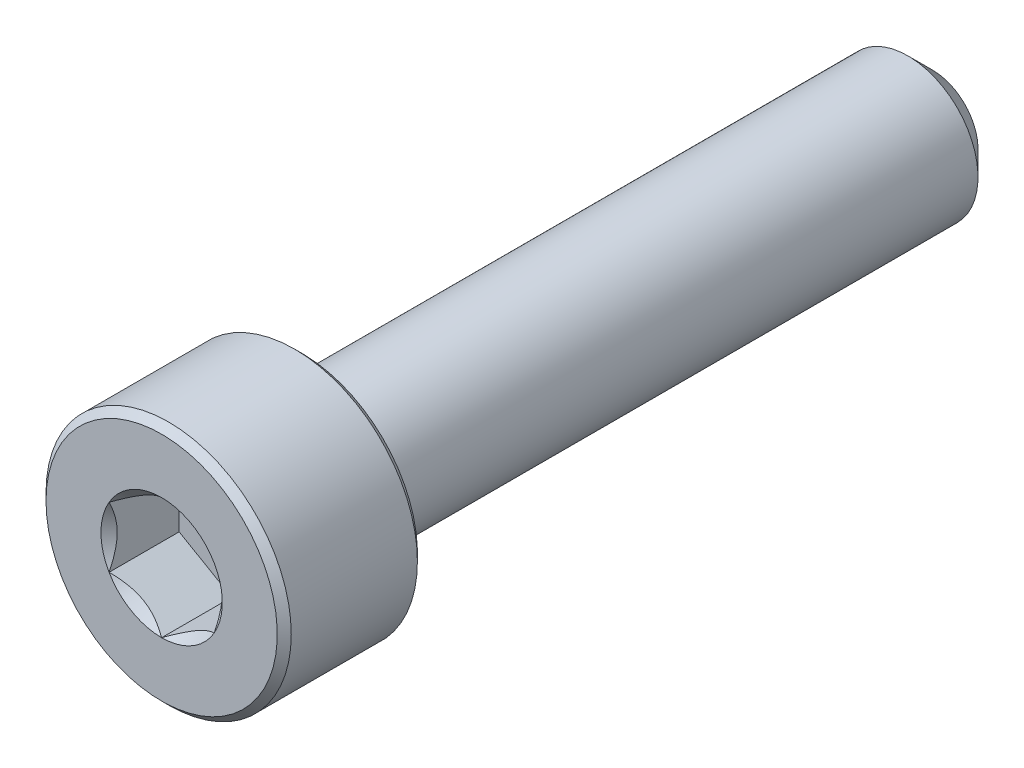
SolidWorks part; units mm, degrees
material "Plain Carbon Steel"
ref_plane "Front Plane" through (0, 0, 0) normal (0, 0, 1) x (1, 0, 0)
ref_plane "Top Plane" through (0, 0, 0) normal (0, 1, 0) x (1, 0, 0)
ref_plane "Right Plane" through (0, 0, 0) normal (1, 0, 0) x (0, 0, -1)
sketch "Sketch1" plane through (0, 0, 0) normal (1, 0, 0) x (0, 0, -1)
  line L0 (-11, 0) -> (11, 0) construction
  line L1 (11, 0) -> (11, 1.3) construction
  line L2 (11, 1.3) -> (10.3, 2) construction
  line L3 (10.3, 2) -> (-7, 2) construction
  line L5 (-7, 2) -> (-7, 3.5) construction
  line L6 (-7, 3.5) -> (-11, 3.5) construction
  line L7 (-11, 3.5) -> (-11, 0) construction
  line L8 (11, 1.3) -> (11, 2) construction
  line L9 (10.9563, 2.0758) -> (11.3063, 1.4696) construction
  line L10 (11.3063, 1.4696) -> (11.6562, 2.0758) construction
  line L11 (11.6562, 2.0758) -> (10.9563, 2.0758) construction
  line L12 (11.3063, 2.0758) -> (11.3063, 2) construction
  line L13 (11.3063, 1.4696) -> (11.3063, 1.5453) construction
  line L14 (11.2625, 1.5453) -> (11.35, 1.5453) construction
  line L15 (11, 2) -> (11.6125, 2) construction
  line L16 (10.9781, 2.0379) -> (11.6344, 2.0379) construction
  line L17 (11, 0) -> (11, -2) construction
  line L18 (-7.2, 3.5) -> (-7, 3.3) construction
  line L19 (-10.8, 3.5) -> (-11, 3.3) construction
  point P0 (-11, 1.5)
  point P3 (8.55, 2)
  point P4 (0, 0)
  point P22 (11.3063, 1.5453)
  point P24 (-7, 2)
  point P25 (11.3063, 2)
  point P28 (11.3063, 2.0379)
  point P29 (8.55, -2)
  point P31 (-9, 3.5)
  point P37 (-7.7, 3.5)
  point P38 (-10.7, 3.5)
  point P41 (-9, 0)
  dimension "head height" = 4
  dimension "D1" = 45
  dimension "Head Diameter" = 7
  dimension "Thread Size" = 4
  dimension "drive size" = 3
  dimension "Thread Pitch" = 0.7
  dimension "D2" = 0.0875
  dimension "D3" = 0.7
  dimension "D4" = 2.45
  dimension "D7" = 0.2
  dimension "D8" = 0.2
  dimension "D9" = 0.2
  dimension "D10" = 0.1
  dimension "D11" = 0.5
  dimension "length" = 18
  dimension "Drive Depth" = 2
sketch "Sketch2" plane through (0, 0, 0) normal (1, 0, 0) x (0, 0, -1)
  line L1 (-10.8, 3.5) -> (-7.2, 3.5)
  line L4 (10.3, 2) -> (11, 1.3)
  line L5 (11, 1.3) -> (11, 0)
  line L6 (-7.2, 3.5) -> (-7, 3.3) construction
  line L7 (11, 0) -> (-11, 0)
  line L8 (-10.8, 3.5) -> (-11, 3.3) construction
  line L9 (-7.2, 3.5) -> (-7, 3.3)
  line L10 (-10.8, 3.5) -> (-11, 3.3)
  line L11 (-11, 3.3) -> (-11, 0)
  line L12 (-7, 3.3) -> (-7, 2)
  line L13 (-7, 2) -> (10.3, 2)
revolve "Revolve1" add sketch "Sketch2" angle 360 about L7
sketch "Sketch3" plane through (0, 0, 11) normal (0, 0, 1) x (1, 0, 0)
  line L1 (0, 1.7321) -> (-1.5, 0.866)
  line L2 (-1.5, 0.866) -> (-1.5, -0.866)
  line L3 (-1.5, -0.866) -> (0, -1.7321)
  line L4 (0, -1.7321) -> (1.5, -0.866)
  line L5 (1.5, -0.866) -> (1.5, 0.866)
  line L6 (1.5, 0.866) -> (0, 1.7321)
  circle A0 centre (0, 0) radius 1.5 construction
  dimension "D1" = 3
extrude "Cut-Extrude1" cut sketch "Sketch3" against normal up to vertex (2 mm away) up to point (0, 0, 9)
sketch "Sketch4" plane through (0, 0, 11) normal (0, 0, 1) x (1, 0, 0)
  circle A0 centre (0, 0) radius 1.7321
extrude "Cut-Extrude2" cut sketch "Sketch4" against normal blind 0.5 draft 45
ref_plane "Plane1" [suppressed] through (0, 0, 7) normal (0, 0, 1) x (1, 0, 0)
split "Split1" [suppressed] bodies to split 106
sketch "Sketch6" [suppressed] plane through (0, 0, -11) normal (0, 0, -1) x (-1, 0, 0)
  circle A0 centre (0, 0) radius 2
curve "Helix/Spiral1" [suppressed] pitch 0.7 height 18.7 turns 26.7143
sketch "Sketch7" [suppressed] plane through (0, 0, 0) normal (1, 0, 0) x (0, 0, -1)
  line L0 (10.9781, 2.0379) -> (11.6344, 2.0379)
  line L1 (11.6344, 2.0379) -> (11.35, 1.5453)
  line L2 (11.35, 1.5453) -> (11.2625, 1.5453)
  line L3 (11.2625, 1.5453) -> (10.9781, 2.0379)
sweep "Cut-Sweep1" [suppressed] cut profiles "Sketch7" path "Helix/Spiral1"
sketch "Sketch8" [suppressed] plane through (0, 0, 7) normal (0, 0, -1) x (-1, 0, 0)
  circle A0 centre (0, 0) radius 2
extrude "Boss-Extrude1" [suppressed] add sketch "Sketch8" along normal through all draft 45
ref_plane "Plane2" [suppressed] through (0, 0, 9) normal (0, 0, 1) x (1, 0, 0)
sketch "Sketch9" [suppressed] plane through (0, 0, 9) normal (0, 0, 1) x (1, 0, 0)
  line L0 (0, 3.4038) -> (0.0916, 3.4988)
  line L1 (0, 3.4038) -> (-0.0916, 3.4988)
  line L2 (0, 3.5) -> (0, 0) construction
  line L3 (-0.0916, 3.4988) -> (0, 0) construction
  line L4 (0, 0) -> (0.0916, 3.4988) construction
  arc A0 (0.0916, 3.4988) -> (-0.0916, 3.4988) centre (0, 0) ccw
  circle A1 centre (0, 0) radius 3.4038 construction
  dimension "D1" = 7
  dimension "D2" = 6.8075
  dimension "D3" = 3
extrude "Cut-Extrude4" [suppressed] cut sketch "Sketch9" against normal up to vertex and the other way up to vertex
pattern_circular "CirPattern2" [suppressed] count 96 over 360 about axis through (0, 0, 11) along (0, 0, -1) of bodies 113
equation "\"D2@Sketch1\" = \"Thread Pitch@Sketch1\" / 8"
equation "\"D3@Sketch1\" = \"Thread Pitch@Sketch1\""
equation "\"D3@Helix/Spiral1\" = \"length@Sketch1\" + \"Thread Pitch@Sketch1\""
equation "\"D4@Helix/Spiral1\" = \"Thread Pitch@Sketch1\""
equation "\"D4@Sketch1\" = \"Thread Pitch@Sketch1\" * 3.5"
equation "\"D7@Sketch1\"=\"head height@Sketch1\"*.05"
equation "\"D8@Sketch1\"=\"D7@Sketch1\""
equation "\"D9@Sketch1\"=\"D7@Sketch1\""
equation "\"D10@Sketch1\"=\"D7@Sketch1\"/2"
equation "\"D11@Sketch1\"=\"D10@Sketch1\"*5"
equation "\"D1@CirPattern2\"=( 360 / \"D3@Sketch9\" )*0.8"
equation "\"D1@Sketch3\" = \"drive size@Sketch1\""
equation "\"D2@Sketch9\"=\"Head Diameter@Sketch1\" * 0.9725"
